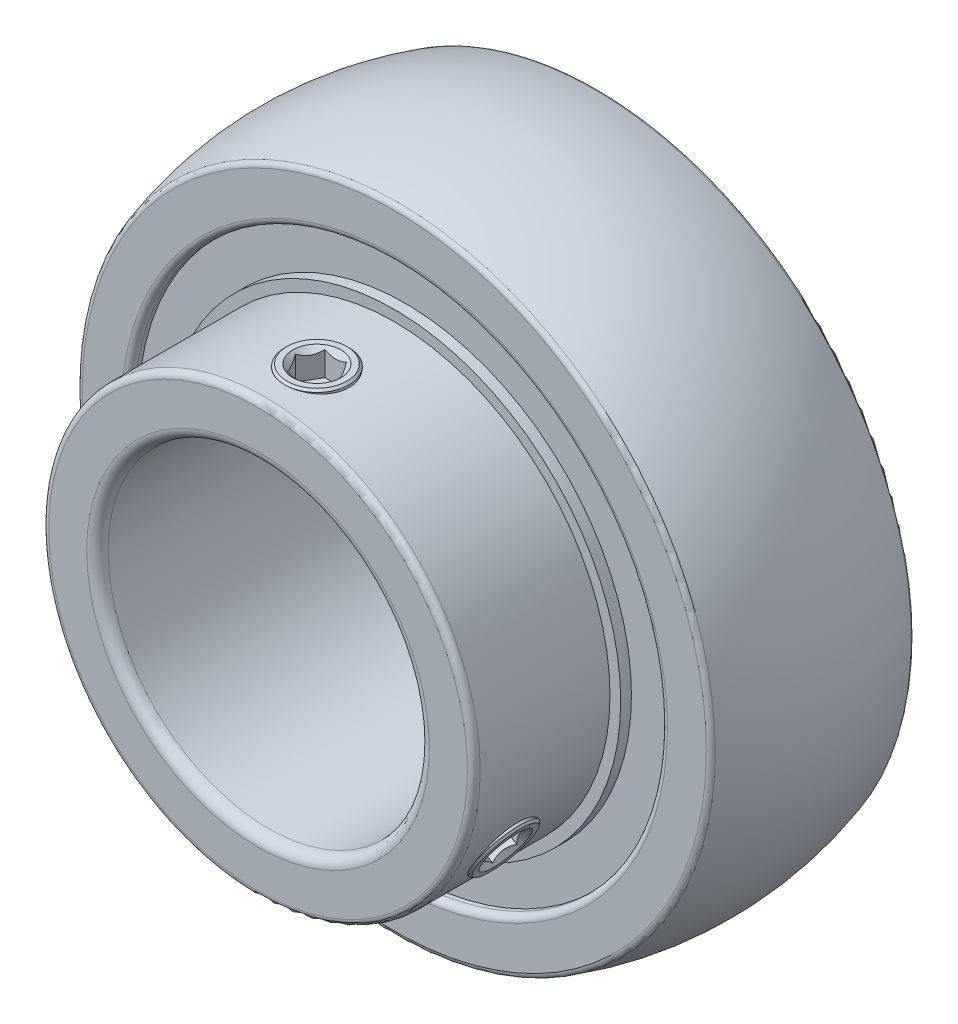
SolidWorks part; units mm, degrees
material "AISI 52100 (100Cr6)"
ref_plane "Plano frontal" through (0, 0, 0) normal (0, 0, 1) x (1, 0, 0)
ref_plane "Plano superior" through (0, 0, 0) normal (0, 1, 0) x (1, 0, 0)
ref_plane "Plano direito" through (0, 0, 0) normal (1, 0, 0) x (0, 0, -1)
sketch "Esboço1" plane through (0, 0, 0) normal (1, 0, 0) x (0, 0, -1)
  line L0 (-996.83, 0) -> (49003.17, 0) construction
  line L1 (-9.5, 29.1419) -> (-9.5, 25.51)
  line L2 (9.5, 20.15) -> (9.5, 21.15)
  line L3 (9.5, 21.15) -> (8.5, 21.15)
  line L4 (8.5, 21.15) -> (8.5, 24.91)
  line L5 (-22.22, 19.55) -> (-22.22, 16)
  line L6 (-21.22, 15) -> (14.88, 15)
  line L7 (15.88, 16) -> (15.88, 19.55)
  line L8 (15.28, 20.15) -> (9.5, 20.15)
  line L9 (-8.9, 24.91) -> (-8.5, 24.91)
  line L10 (8, 24.91) -> (8, 20.15)
  line L11 (-8, 24.91) -> (-8, 20.15)
  line L12 (9.5, 25.51) -> (9.5, 29.1419)
  line L13 (0, 0) -> (0, 31) construction
  line L14 (-8.5, 21.15) -> (-8.5, 24.91)
  line L15 (-9.5, 21.15) -> (-8.5, 21.15)
  line L16 (-9.5, 20.15) -> (-9.5, 21.15)
  line L17 (-8, 24.91) -> (8, 24.91)
  line L18 (-9.5, 20.15) -> (-21.62, 20.15)
  line L19 (8, 20.15) -> (-8, 20.15)
  line L20 (8.5, 24.91) -> (8.9, 24.91)
  arc A0 (-9.1475, 29.6196) -> (9.1475, 29.6196) centre (0, 0) cw
  arc A1 (-9.5, 25.51) -> (-8.9, 24.91) centre (-8.9, 25.51) ccw
  arc A2 (8.9, 24.91) -> (9.5, 25.51) centre (8.9, 25.51) ccw
  arc A3 (15.88, 19.55) -> (15.28, 20.15) centre (15.28, 19.55) ccw
  arc A4 (-21.62, 20.15) -> (-22.22, 19.55) centre (-21.62, 19.55) ccw
  arc A5 (14.88, 15) -> (15.88, 16) centre (14.88, 16) ccw
  arc A6 (-22.22, 16) -> (-21.22, 15) centre (-21.22, 16) ccw
  arc A7 (9.1475, 29.6196) -> (9.5, 29.1419) centre (9, 29.1419) cw
  arc A8 (-9.1475, 29.6196) -> (-9.5, 29.1419) centre (-9, 29.1419) ccw
  dimension "D6" = 0.6
  dimension "D7" = 1
  dimension "D15" = 0.5
  dimension "D11" = 62
  dimension "D2" = 1.5
  dimension "D3" = 19
  dimension "D4" = 38.1
  dimension "D5" = 15.88
  dimension "D8" = 0.5
  dimension "D10" = 30
  dimension "D12" = 49.82
  dimension "D13" = 40.3
revolve "Revolução1" add sketch "Esboço1" angle 360 about L0
sketch "Esboço2" plane through (0, 0, 0) normal (0, 1, 0) x (1, 0, 0)
  line L0 (-19.55, -22.22) -> (19.55, -22.22) construction
  circle A0 centre (0, -16.72) radius 3
  dimension "D1" = 6
  dimension "D2" = 5.5
extrude "Corte-extrusão1" cut sketch "Esboço2" along normal through all
sketch "Esboço3" plane through (0, 0, 0) normal (1, 0, 0) x (0, 0, -1)
  line L0 (-16.72, -1000.5881) -> (-16.72, 48999.4119) construction
  line L1 (-19.52, 20.35) -> (-19.72, 20.15)
  line L2 (-18.97, 20.35) -> (-19.52, 20.35)
  line L3 (-16.72, 17.85) -> (-16.72, 15)
  line L4 (-16.72, 15) -> (-19.12, 15)
  line L5 (-19.72, 20.15) -> (-19.72, 15.6)
  line L6 (-19.72, 15.6) -> (-19.12, 15)
  line L7 (-18.97, 20.35) -> (-18.47, 19.85)
  line L8 (-18.47, 19.85) -> (-18.47, 17.85)
  line L9 (-18.47, 17.85) -> (-16.72, 17.85)
  line L10 (-21.22, 15) -> (14.88, 15) construction
  line L11 (-9.5, 20.15) -> (-21.62, 20.15) construction
  dimension "D1" = 0.2
  dimension "D5" = 2.5
  dimension "D6" = 45
  dimension "D7" = 0.6
  dimension "D8" = 6
  dimension "D9" = 3.5
  dimension "D10" = 4.5
revolve "Revolução2" add sketch "Esboço3" angle 360 about L0
sketch "Esboço4" plane through (0, 20.35, 0) normal (0, 1, 0) x (1, 0, 0)
  line L1 (1.0104, -18.47) -> (2.0207, -16.72)
  line L2 (2.0207, -16.72) -> (1.0104, -14.97)
  line L3 (1.0104, -14.97) -> (-1.0104, -14.97)
  line L4 (-1.0104, -14.97) -> (-2.0207, -16.72)
  line L5 (-2.0207, -16.72) -> (-1.0104, -18.47)
  line L6 (-1.0104, -18.47) -> (1.0104, -18.47)
  circle A0 centre (0, -16.72) radius 1.75 construction
  circle A2 centre (0, -16.72) radius 1.75 construction
extrude "Corte-extrusão2" cut sketch "Esboço4" against normal up to vertex up to point (0, 17.85, 18.47)
pattern_circular "PadrãoCircular1" count 2 over 120 about axis through (0, 0, 996.83) along (0, 0, 1) of "Revolução2", "Corte-extrusão2", "Corte-extrusão1" reverse direction yes
